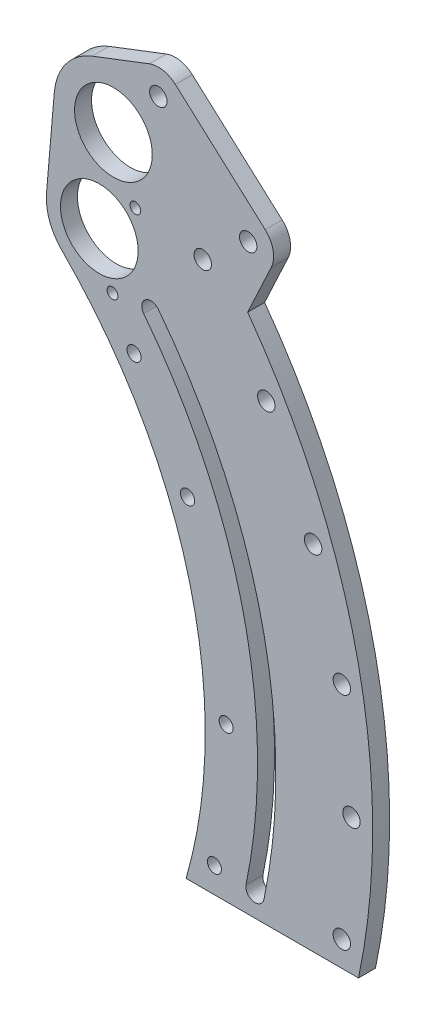
SolidWorks part; units mm, degrees
material "6061-T6 (SS)"
ref_plane "Front Plane" through (0, 0, 0) normal (0, 0, 1) x (1, 0, 0)
ref_plane "Top Plane" through (0, 0, 0) normal (0, 1, 0) x (1, 0, 0)
ref_plane "Right Plane" through (0, 0, 0) normal (1, 0, 0) x (0, 0, -1)
sketch "Sketch1" plane through (0, 0, 0) normal (0, 0, 1) x (1, 0, 0)
  line L0 (0, 0) -> (177.8, 0) construction
  line L1 (177.8, 0) -> (183.3563, 0) construction
  line L2 (0, 0) -> (191.1772, 6.6761) construction
  line L3 (0, 0) -> (182.7798, 182.7798) construction
  line L4 (184.7031, 10.1184) -> (184.959, 2.7905) construction
  line L5 (184.959, 2.7905) -> (191.4331, -0.6518) construction
  line L6 (191.4331, -0.6518) -> (197.6513, 3.2337) construction
  line L7 (197.6513, 3.2337) -> (197.3954, 10.5616) construction
  line L8 (197.3954, 10.5616) -> (190.9213, 14.0039) construction
  line L9 (190.9213, 14.0039) -> (184.7031, 10.1184) construction
  line L10 (156.6987, 109.7216) -> (0, 0) construction
  line L11 (0, 0) -> (176.7324, 73.2049) construction
  line L12 (183.3563, 0) -> (183.3563, -50.8) construction
  line L13 (176.1785, -50.8) -> (183.3563, -50.8) construction
  line L14 (0, 0) -> (186.7878, -41.275) construction
  line L15 (0, 0) -> (203.2, 0) construction
  line L16 (203.2, 0) -> (209.55, 0) construction
  line L17 (209.55, 0) -> (228.6, 0) construction
  line L18 (228.6, 0) -> (238.125, 0) construction
  line L19 (0, 0) -> (238.125, 0) construction
  line L20 (0, 0) -> (234.5073, 41.35) construction
  line L21 (176.1785, -50.8) -> (240.7615, -50.8)
  line L22 (0, 0) -> (238.125, 0) construction
  line L23 (0, 0) -> (234.5073, -41.35) construction
  line L24 (129.6524, 129.6524) -> (173.9925, 173.9925)
  line L25 (165.5338, 128.4903) -> (160.5177, 124.5966) construction
  line L26 (198.8628, -41.7593) -> (205.1195, -42.8625) construction
  arc A0 (183.3563, 0) -> (129.6524, 129.6524) centre (0, 0) ccw
  arc A1 (184.9438, 0) -> (130.775, 130.775) centre (0, 0) ccw construction
  circle A3 centre (191.1772, 6.6761) radius 6.35 construction
  circle A4 centre (191.1772, 6.6761) radius 2.6289
  circle A5 centre (156.6987, 109.7216) radius 2.6289
  circle A6 centre (176.7324, 73.2049) radius 2.667
  arc A7 (183.3563, 0) -> (176.1785, -50.8) centre (0, 0) cw
  circle A8 centre (186.7878, -41.275) radius 2.6289
  arc A9 (203.2, 0) -> (143.6841, 143.6841) centre (0, 0) ccw construction
  arc A10 (209.55, 0) -> (148.1742, 148.1742) centre (0, 0) ccw construction
  arc A11 (228.6, 0) -> (161.6446, 161.6446) centre (0, 0) ccw construction
  arc A12 (238.125, 0) -> (168.3798, 168.3798) centre (0, 0) ccw construction
  circle A13 centre (238.125, 0) radius 3.2639
  circle A14 centre (234.5073, 41.35) radius 3.2639
  circle A15 centre (223.7643, 81.4435) radius 3.2639
  circle A16 centre (206.2223, 119.0625) radius 3.2639
  circle A17 centre (182.4143, 153.0638) radius 3.2639
  arc A18 (240.7615, -50.8) -> (173.9925, 173.9925) centre (0, 0) ccw
  circle A19 centre (234.5073, -41.35) radius 3.2639
  arc A20 (209.55, 0) -> (165.5338, 128.4903) centre (0, 0) ccw construction
  arc A21 (160.5177, 124.5966) -> (203.2, 0) centre (0, 0) cw construction
  arc A22 (209.55, 0) -> (205.1195, -42.8625) centre (0, 0) cw construction
  arc A23 (203.2, 0) -> (198.8628, -41.7593) centre (0, 0) cw construction
  arc A24 (165.5338, 128.4903) -> (160.5177, 124.5966) centre (163.0257, 126.5435) ccw construction
  arc A25 (205.1195, -42.8625) -> (198.8628, -41.7593) centre (201.9911, -42.3109) cw construction
  arc A26 (202.946, 0) -> (198.6134, -41.711) centre (0, 0) cw
  arc A27 (205.3689, -42.9106) -> (198.6134, -41.711) centre (201.9911, -42.3109) cw
  arc A28 (209.804, 0) -> (205.3689, -42.9106) centre (0, 0) cw
  arc A29 (209.804, 0) -> (165.7345, 128.646) centre (0, 0) ccw
  arc A30 (165.7345, 128.646) -> (160.317, 124.4409) centre (163.0257, 126.5435) ccw
  arc A31 (160.317, 124.4409) -> (202.946, 0) centre (0, 0) cw
  point P9 (151.4971, 106.0794)
  point P20 (170.8657, 70.7749)
  point P27 (179.0372, -39.5623)
  dimension "D3" = 1.5875
  dimension "D4" = 12.7
  dimension "D6" = 5.2578
  dimension "D8" = 5.2578
  dimension "D12" = 5.334
  dimension "D14" = 50.8
  dimension "D15" = 5.2578
  dimension "D19" = 6.35
  dimension "D20" = 19.05
  dimension "D22" = 6.5278
  dimension "D26" = 7.9375
  dimension "D30" = 25.4
  dimension "D31" = 7.9375
  dimension "D33" = 183.3562
  dimension "D1" = 177.8
  dimension "D2" = 5.5562
  dimension "D5" = 2
  dimension "D7" = 45
  dimension "D9" = 6.35
  dimension "D10" = 10
  dimension "D11" = 22.5
  dimension "D13" = 6.35
  dimension "D16" = 9.525
  dimension "D17" = 7.9375
  dimension "D18" = 203.2
  dimension "D21" = 9.525
  dimension "D24" = 10
  dimension "D25" = 238.125
  dimension "D28" = 10
  dimension "D29" = 238.125
  dimension "D32" = 0.254
  dimension "D23" = 5
  dimension "D27" = 2
extrude "Boss-Extrude1" add sketch "Sketch1" along normal blind 6.35 contours L21 A18 L24 A0 A7 A19 A4 A5 A6 A8 A13 A14 A15 A16 A17 A22 A25 A23 A21 A24 A20 region at (184.0595, -26.0065, 0)
sketch "Sketch2" plane through (0, 0, 6.35) normal (0, 0, 1) x (1, 0, 0)
  line L0 (0, 0) -> (125.7236, 125.7236) construction
  line L1 (0, 0) -> (183.3562, 0) construction
  line L2 (125.7236, 125.7236) -> (143.6841, 143.6841) construction
  line L3 (129.6524, 129.6524) -> (173.9925, 173.9925) construction
  line L4 (143.6841, 143.6841) -> (148.964, 177.5652) construction
  line L6 (0, 0) -> (148.964, 177.5652) construction
  arc A0 (176.1785, -50.8) -> (129.6524, 129.6524) centre (0, 0) ccw construction
  circle A1 centre (143.6841, 143.6841) radius 14.5542
  circle A2 centre (143.6841, 143.6841) radius 25.4 construction
  circle A3 centre (143.6841, 143.6841) radius 11.43 construction
  circle A4 centre (143.6841, 143.6841) radius 19.05 construction
  circle A5 centre (148.964, 177.5652) radius 22.86 construction
  circle A6 centre (148.964, 177.5652) radius 14.5542
  dimension "D4" = 29.1084
  dimension "D5" = 50.8
  dimension "D6" = 22.86
  dimension "D7" = 38.1
  dimension "D8" = 45.72
  dimension "D9" = 231.775
  dimension "D10" = 29.1084
  dimension "D1" = 177.8
  dimension "D2" = 45
  dimension "D3" = 25.4
  dimension "D11" = 34.29
sketch "Sketch3" plane through (0, 0, 6.35) normal (0, 0, 1) x (1, 0, 0)
  line L0 (129.6524, 129.6524) -> (173.9925, 173.9925) construction
  line L1 (129.6524, 129.6524) -> (161.6446, 161.6446)
  line L4 (123.9121, 145.3706) -> (126.8194, 179.454)
  line L5 (161.6446, 161.6446) -> (173.9925, 173.9925)
  line L6 (0, 0) -> (199.4397, 167.3498) construction
  line L7 (0, 0) -> (183.3562, 0) construction
  line L9 (208.0723, 163.3243) -> (199.2435, 144.391)
  line L10 (148.964, 177.5652) -> (165.7989, 197.6325) construction
  line L11 (0, 0) -> (148.964, 177.5652) construction
  line L12 (140.998, 198.3135) -> (162.385, 206.5246)
  line L13 (172.1715, 204.7117) -> (205.8123, 174.429)
  arc A1 (129.6524, 129.6524) -> (123.9121, 145.3706) centre (143.6841, 143.6841) cw
  arc A2 (140.998, 198.3135) -> (126.8194, 179.454) centre (148.964, 177.5652) ccw
  circle A3 centre (148.964, 177.5652) radius 14.5542
  circle A4 centre (199.4397, 167.3498) radius 3.2639
  arc A5 (208.0723, 163.3243) -> (205.8123, 174.429) centre (199.4397, 167.3498) ccw
  arc A7 (173.9925, 173.9925) -> (199.2435, 144.391) centre (0, 0) cw
  arc A8 (240.7615, -50.8) -> (173.9925, 173.9925) centre (0, 0) ccw construction
  circle A9 centre (165.7989, 197.6325) radius 9.525 construction
  circle A10 centre (148.964, 177.5652) radius 16.1417 construction
  circle A11 centre (165.7989, 197.6325) radius 3.2639
  arc A12 (162.385, 206.5246) -> (172.1715, 204.7117) centre (165.7989, 197.6325) cw
  dimension "D1" = 25.4
  dimension "D2" = 29.1084
  dimension "D3" = 22.225
  dimension "D5" = 260.35
  dimension "D6" = 6.5278
  dimension "D7" = 9.525
  dimension "D8" = 25
  dimension "D9" = 19.05
  dimension "D10" = 1.5875
  dimension "D11" = 6.5278
  dimension "D12" = 9.525
  dimension "D4" = 40
  dimension "D13" = 26.1937
extrude "Boss-Extrude2" add sketch "Sketch3" against normal blind 6.35
sketch "Sketch4" plane through (0, 0, 6.35) normal (0, 0, 1) x (1, 0, 0)
  line L0 (143.6841, 143.6841) -> (157.1545, 157.1545) construction
  line L1 (125.7236, 125.7236) -> (143.6841, 143.6841) construction
  line L2 (143.6841, 143.6841) -> (148.6146, 125.2832) construction
  circle A0 centre (143.6841, 143.6841) radius 14.5542
  circle A1 centre (157.1545, 157.1545) radius 2.0193
  circle A2 centre (148.6146, 125.2832) radius 2.0193
  dimension "D1" = 29.1084
  dimension "D2" = 4.0386
  dimension "D4" = 4.0386
  dimension "D3" = 19.05
  dimension "D5" = 19.05
  dimension "D6" = 60
extrude "Cut-Extrude1" cut sketch "Sketch4" against normal through all
